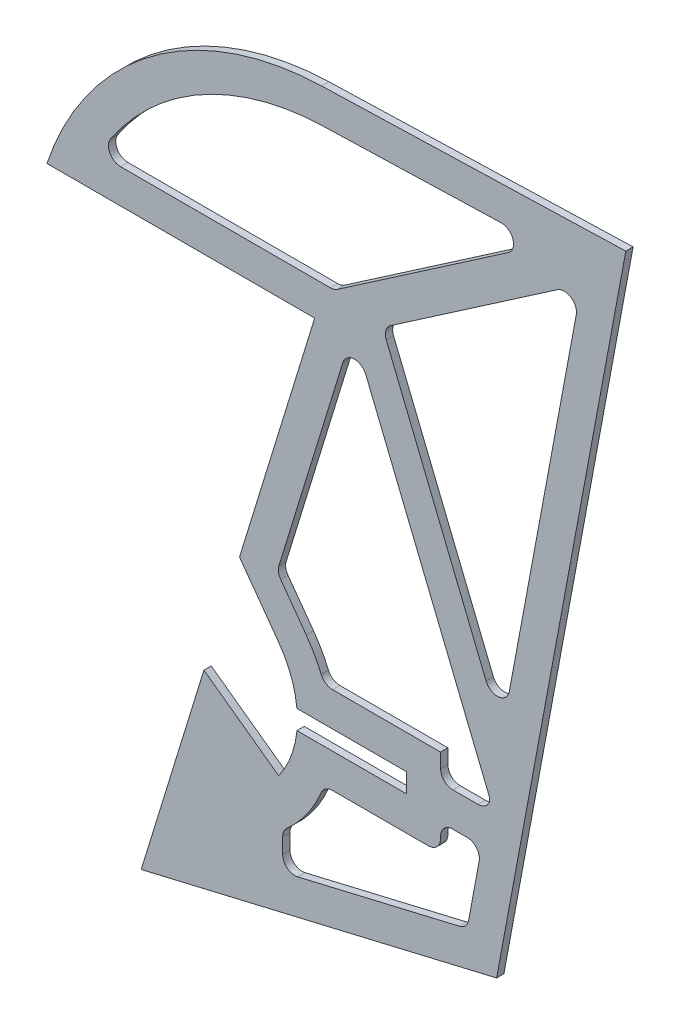
SolidWorks part; units mm, degrees
ref_plane "Front Plane" through (0, 0, 0) normal (0, 0, 1) x (1, 0, 0)
ref_plane "Top Plane" through (0, 0, 0) normal (0, 1, 0) x (1, 0, 0)
ref_plane "Right Plane" through (0, 0, 0) normal (1, 0, 0) x (0, 0, -1)
sketch "Sketch1" plane through (0, 0, 0) normal (0, 0, 1) x (1, 0, 0)
  line L0 (0, 0) -> (-50000, 0) construction
  line L1 (0, -1) -> (-11.43, -1) construction
  line L2 (0, -1) -> (0, 1) construction
  line L3 (0, 1) -> (-11.43, 1) construction
  line L4 (-11.43, -1) -> (-11.43, 1) construction
  line L7 (-17.0388, 37.195) -> (-24.8853, 11.6793)
  line L8 (-35.1436, -21.6791) -> (1.9402, -12.9383)
  line L9 (1.9402, -12.9383) -> (15.4182, 59.4781)
  line L10 (-17.0388, 37.195) -> (-44.9788, 37.195)
  line L11 (15.4182, 59.4781) -> (-16.3177, 58.531)
  line L12 (-20.7991, -6.0325) -> (-28.5968, -0.3899)
  line L13 (15.4182, 59.4781) -> (-17.0388, 37.195) construction
  line L14 (-18.8941, 1) -> (-7.4641, 1)
  line L15 (-18.8941, 1) -> (-18.8941, -1) construction
  line L16 (-18.8941, -1) -> (-7.4641, -1)
  line L17 (-7.4641, 1) -> (-7.4641, -1)
  line L18 (-18.8941, 1) -> (-7.4641, -1) construction
  line L19 (-18.8941, -1) -> (-7.4641, 1) construction
  line L20 (-20.7991, 6.0325) -> (-24.8853, 11.6793)
  line L21 (-20.7991, -6.0325) -> (-23.1678, -9.3059) construction
  line L22 (-28.5968, -0.3899) -> (-35.1436, -21.6791)
  arc A1 (-44.9788, 37.195) -> (-16.3177, 58.531) centre (-15.3875, 27.3628) cw
  arc A2 (-20.7991, -6.0325) -> (-18.8941, -1) centre (-29.1356, 0) ccw
  arc A3 (-18.8941, 1) -> (-20.7991, 6.0325) centre (-29.1356, 0) ccw
  point P4 (0, 0)
  point P14 (-13.1791, 0)
  point P18 (-25.9979, 8.0614)
  dimension "D1" = 2
  dimension "D2" = 11.43
  dimension "D3" = 36.195
  dimension "D4" = 59.69
  dimension "D5" = 40.005
  dimension "D6" = 61.595
  dimension "D7" = 38.1
  dimension "D8" = 73.66
  dimension "D9" = 30.48
  dimension "D10" = 27.94
  dimension "D11" = 11.43
  dimension "D12" = 39.37
  dimension "D13" = 12.065
  dimension "D14" = 31.75
  dimension "D15" = 21.336
  dimension "D16" = 1.905
  dimension "D17" = 12.065
extrude "Boss-Extrude2" add sketch "Sketch1" against normal blind 0.762 contours A1 L10 L7 L8 L9 L11 region at (-10.5723, 24.8286, 0)
sketch "Sketch2" plane through (0, 0, -0.762) normal (0, 0, -1) x (-1, 0, 0)
  line L11 (-15.4182, 59.4781) -> (17.0388, 37.195) construction
  line L12 (3.9081, 0) -> (-4.3483, 0) construction
  line L13 (-1.9402, -12.9383) -> (-15.4182, 59.4781) construction
  line L14 (12.225, 40.751) -> (-4.3483, 0) construction
  line L15 (-16.4245, 58.0123) -> (16.0325, 35.7292)
  line L16 (10.578, 41.4208) -> (-6.9908, -1.778)
  line L17 (3.9081, -1.778) -> (-6.9908, -1.778)
  line L18 (-14.4118, 60.9439) -> (18.0452, 38.6608)
  line L19 (13.872, 40.0812) -> (-1.7058, 1.778)
  line L20 (3.9081, 1.778) -> (-1.7058, 1.778)
  line L21 (-16.4245, 58.0123) -> (-14.4118, 60.9439)
  line L22 (17.9183, 8.1172) -> (20.9654, 12.3281)
  line L23 (20.9654, 12.3281) -> (12.225, 40.751)
  line L24 (12.225, 40.751) -> (39.5526, 40.751)
  line L25 (16.2116, 54.9766) -> (-11.1151, 55.7921)
  line L26 (-11.1151, 55.7921) -> (1.1316, -10.0089)
  line L27 (1.1316, -10.0089) -> (29.9212, -16.7947)
  line L28 (29.9212, -16.7947) -> (26.6577, -6.1824)
  line L29 (26.6577, -6.1824) -> (20.3792, -10.7258)
  line L30 (16.0604, -4.556) -> (3.9081, -4.556)
  line L31 (3.9081, -4.556) -> (3.9081, 4.556)
  line L32 (3.9081, 4.556) -> (16.0604, 4.556)
  line L33 (17.9183, 8.1172) -> (20.9654, 12.3281)
  line L34 (20.9654, 12.3281) -> (12.225, 40.751)
  line L35 (12.225, 40.751) -> (39.5526, 40.751)
  line L36 (16.2116, 54.9766) -> (-11.1151, 55.7921)
  line L37 (-11.1151, 55.7921) -> (1.1316, -10.0089)
  line L38 (1.1316, -10.0089) -> (20.3792, -14.5456)
  line L41 (16.0604, -4.556) -> (3.9081, -4.556)
  line L42 (3.9081, -4.556) -> (3.9081, 4.556)
  line L43 (3.9081, 4.556) -> (16.0604, 4.556)
  line L44 (16.0325, 35.7292) -> (18.0452, 38.6608)
  line L45 (10.578, 41.4208) -> (13.872, 40.0812)
  line L46 (3.9081, -1.778) -> (3.9081, 1.778)
  line L47 (20.3792, -10.7258) -> (20.3792, -14.5456)
  arc A6 (17.9183, 8.1172) -> (16.0604, 4.556) centre (29.1356, 0) ccw
  arc A7 (39.5526, 40.751) -> (16.2116, 54.9766) centre (15.3875, 27.3628) ccw
  arc A8 (16.0604, -4.556) -> (20.3792, -10.7258) centre (29.1356, 0) ccw
  arc A9 (17.9183, 8.1172) -> (16.0604, 4.556) centre (29.1356, 0) ccw
  arc A10 (39.5526, 40.751) -> (16.2116, 54.9766) centre (15.3875, 27.3628) ccw
  arc A11 (16.0604, -4.556) -> (20.3792, -10.7258) centre (29.1356, 0) ccw
  dimension "D1" = 3.556
  dimension "D2" = 1.778
  dimension "D3" = 1.778
extrude "Cut-Extrude1" cut sketch "Sketch2" against normal blind 2.54 contours L35 A10 L36 L18 | L15 L37 L16 | A9 L33 L34 L15 L19 L20 L42 L43 | A11 L41 L42 L17 L37 L38 region at (1.1071, 34.4656, -0.762) region at (-18.1952, 48.0958, -0.762) region at (-10.9361, 15.9471, -0.762) region at (-9.9675, -8.2613, -0.762)
fillet "Fillet1" radius 1.27 19 edges at (-13.1636, 37.6989, -0.381) (-3.9081, -4.556, -0.381) (-1.1316, -10.0089, -0.381) (0.4003, -1.778, -0.381) (-3.9081, -1.778, -0.381) (-16.0604, -4.556, -0.381) (2.4694, 9.3393, -0.381) (-9.959, 39.8989, -0.381) (-3.9081, 1.778, -0.381) (1.0621, 1.778, -0.381) (1.2642, 2.8637, -0.381) (-20.9654, 12.3281, -0.381) (-16.0604, 4.556, -0.381) (-15.0006, 40.751, -0.381) (6.7167, 55.6609, -0.381) (-39.5526, 40.751, -0.381) (10.811, 54.1584, -0.381) (-20.3792, -14.5456, -0.381) (-20.3792, -10.7258, -0.381)
fillet "Fillet2" radius 1.27 1 edges at (-12.9599, 37.8386, -0.381)
